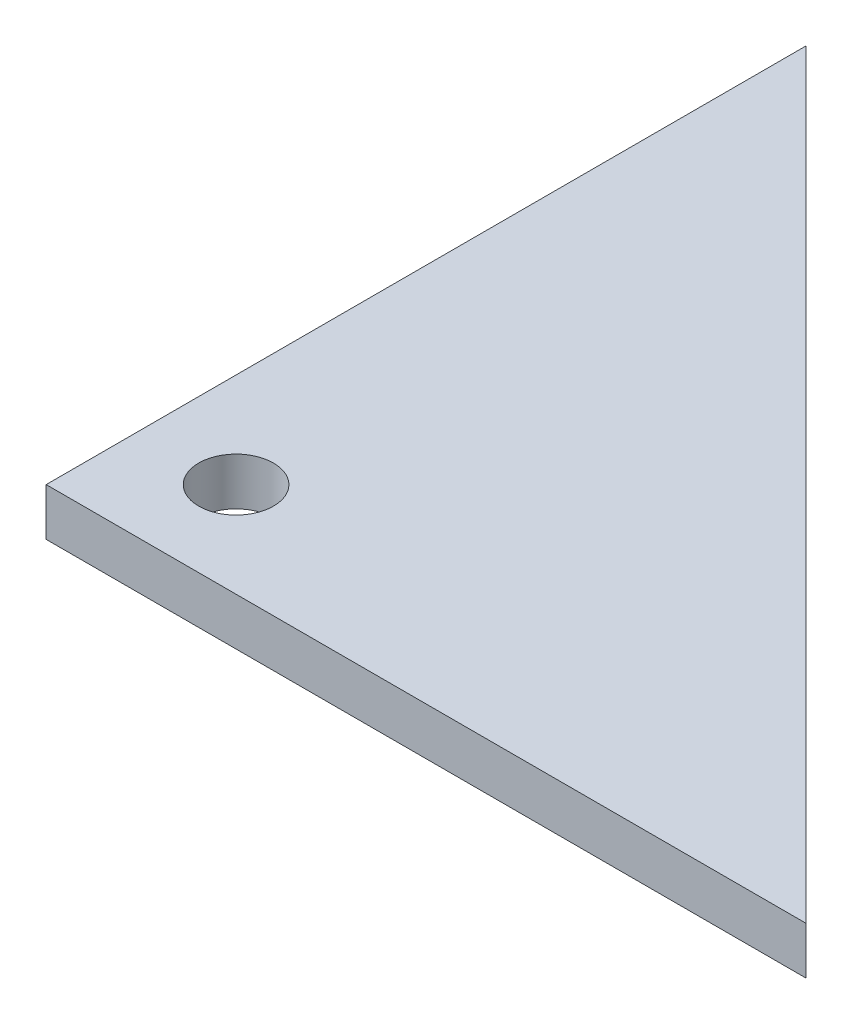
SolidWorks part; units mm, degrees
ref_plane "Front" through (0, 0, 0) normal (0, 0, 1) x (1, 0, 0)
ref_plane "Top" through (0, 0, 0) normal (0, 1, 0) x (1, 0, 0)
ref_plane "Right" through (0, 0, 0) normal (1, 0, 0) x (0, 0, -1)
sketch "Sketch1" plane through (0, 0, 0) normal (0, 1, 0) x (1, 0, 0)
  line L0 (0, 0) -> (50.8, 0)
  line L1 (-21.723, 0) -> (21.723, 0) construction
  line L2 (50.8, 0) -> (0, 50.8)
  line L3 (0, -27.94) -> (0, 27.94) construction
  line L4 (0, 50.8) -> (0, 0)
  dimension "D1" = 50.8
  dimension "D2" = 50.8
extrude "Boss-Extrude1" add sketch "Sketch1" along normal blind 3.175 contours L2 L4 L0
sketch "Sketch2" plane through (0, 3.175, 0) normal (0, 1, 0) x (1, 0, 0)
  line L0 (0, -1.7463) -> (0, 1.7463) construction
  line L1 (-1.7463, 0) -> (1.7463, 0) construction
  circle A0 centre (6.35, 6.35) radius 2.5
  dimension "D1" = 5
  dimension "D3" = 6.35
  dimension "D2" = 6.35
extrude "Cut-Extrude1" cut sketch "Sketch2" against normal through all contours A0
